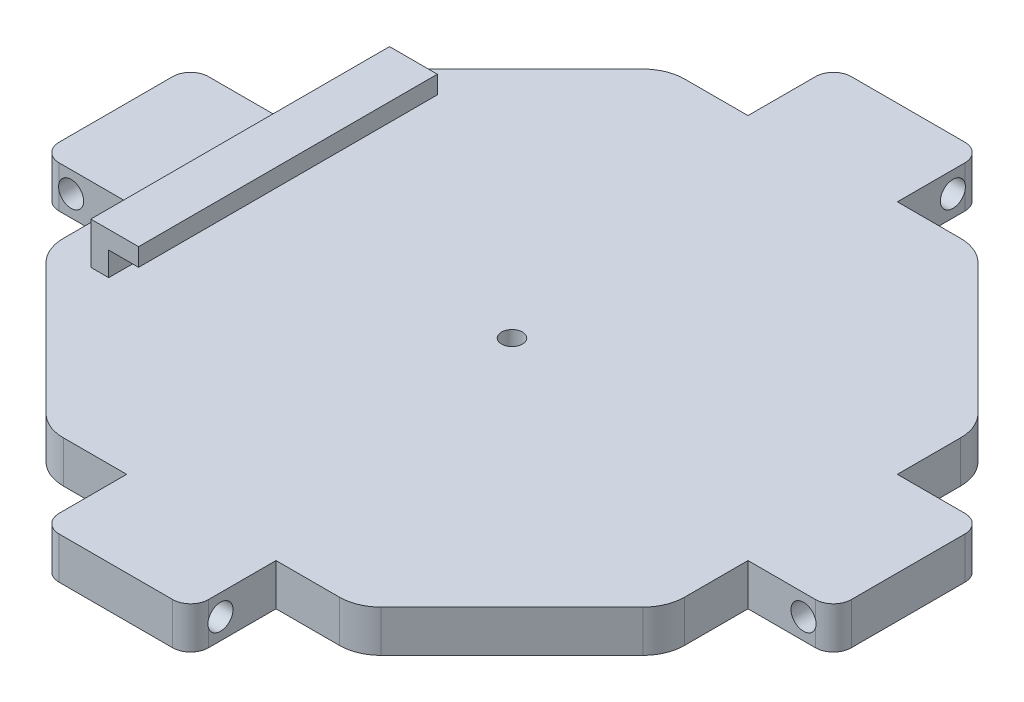
SolidWorks part; units mm, degrees
ref_plane "정면" through (0, 0, 0) normal (0, 0, 1) x (1, 0, 0)
ref_plane "윗면" through (0, 0, 0) normal (0, 1, 0) x (1, 0, 0)
ref_plane "우측면" through (0, 0, 0) normal (1, 0, 0) x (0, 0, -1)
sketch "스케치1" plane through (0, 0, 0) normal (0, 1, 0) x (1, 0, 0)
  line L0 (0, 0) -> (-27.1519, 0) construction
  line L1 (-39, 39) -> (39, 39)
  line L2 (-39, 39) -> (-39, -39)
  line L3 (-39, -39) -> (39, -39)
  line L4 (39, 39) -> (39, -39)
  line L5 (-39, 39) -> (39, -39) construction
  line L6 (-39, -39) -> (39, 39) construction
  line L7 (39, 0) -> (-66.3, 0) construction
  line L8 (-66.3, 0) -> (0, 39) construction
  line L9 (0, 39) -> (0, -39) construction
  line L10 (-26, 39) -> (-39, 26)
  line L11 (-39, -26) -> (-26, -39)
  line L12 (26, -39) -> (39, -26)
  line L13 (26, 39) -> (39, 26)
  line L14 (-26, -52) -> (26, -52)
  line L15 (26, -52) -> (52, -26)
  line L16 (52, -26) -> (52, 26)
  line L17 (52, 26) -> (26, 52)
  line L18 (26, 52) -> (-26, 52)
  line L19 (-26, 52) -> (-52, 26)
  line L20 (-52, 26) -> (-52, -26)
  line L21 (-52, -26) -> (-26, -52)
  line L22 (-52, 12.5) -> (-66.3, 12.5)
  line L23 (-66.3, 12.5) -> (-66.3, -12.5)
  line L24 (-66.3, -12.5) -> (-52, -12.5)
  line L25 (-12.5, -52) -> (-12.5, -66.3)
  line L26 (-12.5, -66.3) -> (12.5, -66.3)
  line L27 (12.5, -66.3) -> (12.5, -52)
  line L28 (52, -12.5) -> (66.3, -12.5)
  line L29 (66.3, -12.5) -> (66.3, 12.5)
  line L30 (66.3, 12.5) -> (52, 12.5)
  line L31 (-12.5, 52) -> (-12.5, 66.3)
  line L32 (-12.5, 66.3) -> (12.5, 66.3)
  line L33 (12.5, 66.3) -> (12.5, 52)
  point P0 (0, 0)
  dimension "D1" = 78
  dimension "D2" = 78
  dimension "D3" = 26
  dimension "D4" = 26
  dimension "D5" = 26
  dimension "D6" = 26
  dimension "D7" = 26
  dimension "D8" = 26
  dimension "D9" = 26
  dimension "D10" = 26
  dimension "D11" = 13
  dimension "D12" = 13
  dimension "D13" = 13
  dimension "D14" = 13
  dimension "D15" = 25
  dimension "D16" = 25
  dimension "D17" = 25
  dimension "D18" = 25
  dimension "D19" = 14.3
  dimension "D20" = 14.3
  dimension "D21" = 14.3
  dimension "D22" = 14.3
  dimension "D23" = 14.3
  dimension "D24" = 12.5
  dimension "D25" = 12.5
  dimension "D26" = 12.5
extrude "보스-돌출1" add sketch "스케치1" along normal blind 7 contours L18 L19 L1 L17 | L10 L1 L2 | L20 L21 L2 L19 | L23 L24 L20 L22 | L33 L32 L31 L18 | L1 L13 L4 | L16 L17 L4 L15 | L29 L30 L16 L28 | L12 L3 L4 | L3 L21 L14 L15 | L11 L2 L3 | L26 L27 L14 L25 region at (0, 0, -45.0667) region at (-34.6667, 0, -34.6667) region at (-45.0667, 0, 0) region at (34.6667, 0, -34.6667) region at (-34.6667, 0, 34.6667) region at (0, 0, -59.15) region at (-59.15, 0, 0) region at (45.0667, 0, 0) region at (0, 0, 45.0667) region at (34.6667, 0, 34.6667) region at (59.15, 0, 0) region at (0, 0, 59.15)
fillet "필렛1" radius 3 8 edges at (-12.5, 3.5, 66.3) (66.3, 3.5, 12.5) (66.3, 3.5, -12.5) (12.5, 3.5, -66.3) (-12.5, 3.5, -66.3) (-66.3, 3.5, -12.5) (-66.3, 3.5, 12.5) (12.5, 3.5, 66.3)
fillet "필렛2" radius 7 8 edges at (26, 3.5, -52) (52, 3.5, -26) (52, 3.5, 26) (26, 3.5, 52) (-26, 3.5, 52) (-52, 3.5, 26) (-52, 3.5, -26) (-26, 3.5, -52)
fillet "필렛3" radius 23 8 edges at (-39, 3.5, 26) (-26, 3.5, 39) (26, 3.5, 39) (39, 3.5, 26) (39, 3.5, -26) (26, 3.5, -39) (-26, 3.5, -39) (-39, 3.5, -26)
sketch "스케치6" plane through (0, 7, 0) normal (0, 1, 0) x (1, 0, 0)
  line L0 (-39, 16.4731) -> (-39, -16.4731) construction
  line L5 (16.4731, 39) -> (-16.4731, 39)
  line L6 (-39, 16.4731) -> (-39, -16.4731)
  line L7 (-16.4731, -39) -> (16.4731, -39)
  line L8 (39, -16.4731) -> (39, 16.4731)
  arc A0 (16.4731, 39) -> (32.4983, 32.4983) centre (16.4731, 16) cw
  arc A1 (32.4983, 32.4983) -> (39, 16.4731) centre (16, 16.4731) cw
  arc A2 (32.4983, -32.4983) -> (39, -16.4731) centre (16, -16.4731) ccw
  arc A3 (32.4983, -32.4983) -> (16.4731, -39) centre (16.4731, -16) cw
  arc A4 (-32.4983, -32.4983) -> (-16.4731, -39) centre (-16.4731, -16) ccw
  arc A5 (-32.4983, -32.4983) -> (-39, -16.4731) centre (-16, -16.4731) cw
  arc A6 (-32.4983, 32.4983) -> (-39, 16.4731) centre (-16, 16.4731) ccw
  arc A7 (-32.4983, 32.4983) -> (-39, 16.4731) centre (-16, 16.4731) ccw construction
  arc A8 (-32.4983, 32.4983) -> (-16.4731, 39) centre (-16.4731, 16) cw
extrude "보스-돌출2" add sketch "스케치6" against normal blind 5
sketch "스케치7" plane through (0, 7, 0) normal (0, 1, 0) x (1, 0, 0)
  circle A0 centre (0, 0) radius 1.75
  dimension "D1" = 3.5
extrude "컷-돌출5" cut sketch "스케치7" against normal through all
sketch "스케치8" plane through (0, 7, 0) normal (0, 1, 0) x (1, 0, 0)
  line L0 (28.0503, -49.9497) -> (49.9497, -28.0503) construction
  line L1 (-39, 39) -> (39, 39)
  line L2 (-39, 39) -> (-39, -39)
  line L3 (-39, -39) -> (39, -39)
  line L4 (39, 39) -> (39, -39)
  line L5 (-39, 39) -> (39, -39) construction
  line L6 (-39, -39) -> (39, 39) construction
  point P0 (0, 0)
sketch "스케치9" plane through (0, 7, 0) normal (0, 1, 0) x (1, 0, 0)
  line L0 (108.4856, 0) -> (-108.4856, 0) construction
  line L1 (-45.5, 25) -> (-42.5, 25)
  line L2 (-45.5, 25) -> (-45.5, -25)
  line L4 (-42.5, 25) -> (-42.5, -25)
  line L5 (-45.5, -25) -> (-42.5, -25)
  dimension "D1" = 42.5
  dimension "D2" = 3
extrude "보스-돌출3" add sketch "스케치9" along normal blind 7
sketch "스케치10" plane through (-42.5, 0, 0) normal (1, 0, 0) x (0, 0, -1)
  line L0 (-25, 14) -> (-25, 7) construction
  line L1 (25, 14) -> (-25, 14)
  line L2 (25, 14) -> (25, 11)
  line L3 (25, 11) -> (-25, 11)
  line L4 (-25, 14) -> (-25, 11)
  dimension "D1" = 3
extrude "보스-돌출4" add sketch "스케치10" along normal blind 5
sketch "스케치11" plane through (0, 0, 12.5) normal (0, 0, 1) x (1, 0, 0)
  line L0 (-66.3, 0) -> (-66.3, 7) construction
  line L1 (-63.3, 7) -> (-52, 7) construction
  line L2 (66.3, 7) -> (66.3, 0) construction
  line L3 (52, 7) -> (63.3, 7) construction
  circle A0 centre (-61.3, 3.5) radius 2.1
  circle A1 centre (61.3, 3.5) radius 2.1
  dimension "D1" = 4.2
  dimension "D6" = 4.2
  dimension "D2" = 5
  dimension "D3" = 3.5
  dimension "D4" = 5
  dimension "D5" = 3.5
extrude "컷-돌출6" cut sketch "스케치11" against normal through all
sketch "스케치12" plane through (-12.5, 0, 0) normal (-1, 0, 0) x (0, 0, 1)
  line L0 (-66.3, 0) -> (-66.3, 7) construction
  line L1 (-52, 7) -> (-63.3, 7) construction
  line L2 (66.3, 7) -> (66.3, 0) construction
  line L3 (63.3, 0) -> (52, 0) construction
  circle A0 centre (-61.3, 3.5) radius 2.1
  circle A1 centre (61.3, 3.5) radius 2.1
  dimension "D3" = 4.2
  dimension "D4" = 4.2
  dimension "D1" = 5
  dimension "D2" = 3.5
  dimension "D5" = 5
  dimension "D6" = 3.5
extrude "컷-돌출7" cut sketch "스케치12" against normal through all
